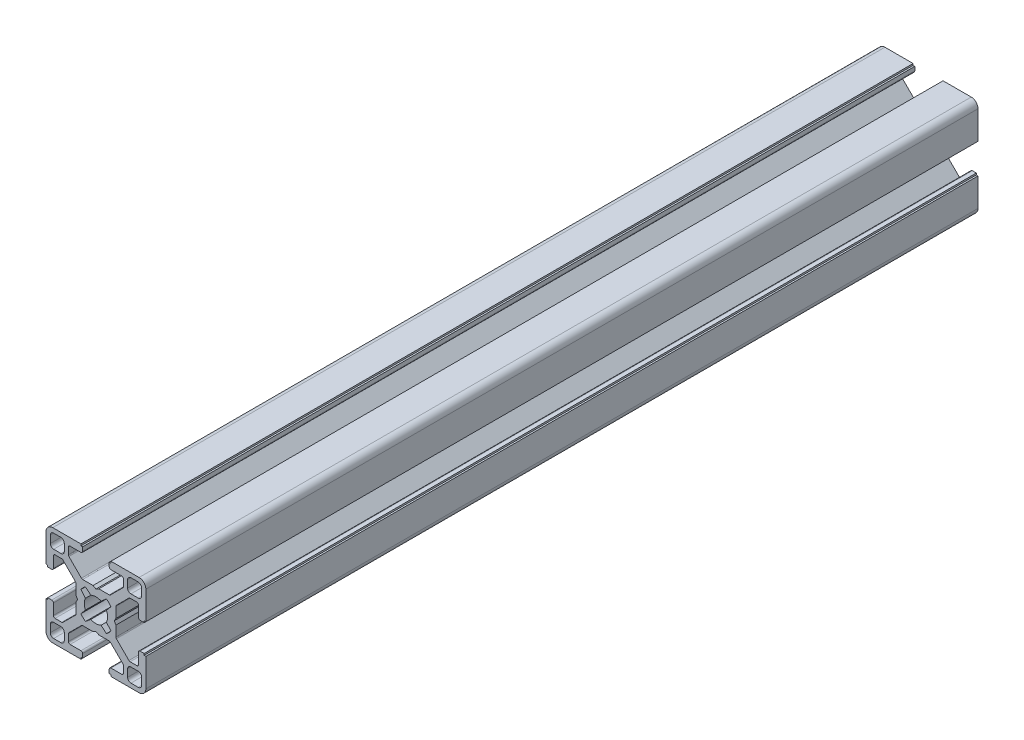
SolidWorks part; units mm, degrees
ref_plane "Front Plane" through (0, 0, 0) normal (0, 0, 1) x (1, 0, 0)
ref_plane "Top Plane" through (0, 0, 0) normal (0, 1, 0) x (1, 0, 0)
ref_plane "Right Plane" through (0, 0, 0) normal (1, 0, 0) x (0, 0, -1)
sketch "Sketch1" plane through (0, 0, 0) normal (0, 0, 1) x (1, 0, 0)
  line L0 (-15, 0) -> (15, 0) construction
  line L1 (0, -15) -> (0, 15) construction
  line L2 (-4.5, 15) -> (4.5, 15) construction
  line L3 (-4, -15) -> (4, -15) construction
  line L4 (-4.5, 15) -> (-4.5, 14.5)
  line L5 (-4.5, 14.5) -> (-4, 14.5)
  line L6 (-4, 14.5) -> (-4, 13.29)
  line L7 (-4.5, 12.79) -> (-7.7675, 12.79)
  line L8 (-8.2675, 12.29) -> (-8.2675, 10.2707)
  line L9 (-8.1211, 9.9171) -> (-4.3504, 6.1464)
  line L10 (-3.9968, 6) -> (0, 6)
  line L11 (0, 0) -> (-15, 15) construction
  line L12 (-4.5, 15) -> (-12.968, 15)
  line L14 (-12.705, 9.5135) -> (-10.5135, 9.5135)
  line L15 (-13.705, 10.5135) -> (-13.705, 12.705)
  line L16 (-12.705, 13.705) -> (-10.5135, 13.705)
  line L17 (-9.5135, 10.5135) -> (-9.5135, 12.705)
  line L18 (-13.705, 9.5135) -> (-9.5135, 13.705) construction
  line L19 (-13.705, 13.705) -> (-9.5135, 9.5135) construction
  line L20 (-3.1568, 4.5038) -> (-1.5303, 3.1477) construction
  line L21 (-4.5038, 3.1568) -> (-3.1477, 1.5303) construction
  line L22 (-6, 3.9968) -> (-6, 0)
  line L23 (-9.9171, 8.1211) -> (-6.1464, 4.3504)
  line L24 (-15, 4.5) -> (-15, 12.968)
  line L25 (-12.29, 8.2675) -> (-10.2707, 8.2675)
  line L26 (-12.79, 4.5) -> (-12.79, 7.7675)
  line L27 (-14.5, 4) -> (-13.29, 4)
  line L28 (-14.5, 4.5) -> (-14.5, 4)
  line L29 (-15, 4.5) -> (-14.5, 4.5)
  circle A0 centre (0, 0) radius 3.5
  arc A1 (-12.968, 15) -> (-15, 12.968) centre (-12.968, 12.968) ccw
  circle A2 centre (0, 0) radius 5.5 construction
  arc A3 (-10.5135, 9.5135) -> (-9.5135, 10.5135) centre (-10.5135, 10.5135) ccw
  arc A4 (-13.705, 12.705) -> (-12.705, 13.705) centre (-12.705, 12.705) cw
  arc A5 (-10.5135, 13.705) -> (-9.5135, 12.705) centre (-10.5135, 12.705) cw
  arc A6 (-12.705, 9.5135) -> (-13.705, 10.5135) centre (-12.705, 10.5135) cw
  arc A7 (-12.79, 4.5) -> (-13.29, 4) centre (-13.29, 4.5) cw
  arc A8 (-12.29, 8.2675) -> (-12.79, 7.7675) centre (-12.29, 7.7675) ccw
  arc A9 (-9.9171, 8.1211) -> (-10.2707, 8.2675) centre (-10.2707, 7.7675) ccw
  arc A10 (-6, 3.9968) -> (-6.1464, 4.3504) centre (-6.5, 3.9968) ccw
  arc A11 (-4.3504, 6.1464) -> (-3.9968, 6) centre (-3.9968, 6.5) ccw
  arc A12 (-4, 13.29) -> (-4.5, 12.79) centre (-4.5, 13.29) cw
  arc A13 (-7.7675, 12.79) -> (-8.2675, 12.29) centre (-7.7675, 12.29) ccw
  arc A14 (-8.2675, 10.2707) -> (-8.1211, 9.9171) centre (-7.7675, 10.2707) ccw
  point P4 (0, 0)
  point P8 (0, 0)
  point P13 (0, 15)
  point P15 (0, -15)
  point P16 (0, 6)
  point P23 (-11.6092, 11.6093)
  point P26 (0, 6)
  point P62 (-12.79, 4)
  point P65 (-12.79, 8.2675)
  point P68 (-10.0636, 8.2675)
  point P71 (-6, 4.2039)
  point P74 (-4.2039, 6)
  point P77 (-4, 12.79)
  point P80 (-8.2675, 12.79)
  point P83 (-8.2675, 10.0636)
  dimension "Center Hole Diameter" = 7
  dimension "D11" = 2.032
  dimension "D9" = 11
  dimension "D13" = 1
  dimension "D14" = 0.5
  dimension "Rail Height" = 30
  dimension "Rail Width" = 30
  dimension "T-Slot Width" = 8
  dimension "T-Slot Depth" = 9
  dimension "D1" = 9
  dimension "D2" = 45
  dimension "D3" = 8
  dimension "D4" = 2.21
  dimension "D5" = 16.535
  dimension "D7" = 2.54
  dimension "D6" = 1.295
  dimension "D8" = 1.246
  dimension "D10" = 10.36
  dimension "D12" = 1.905
sketch "Sketch2" plane through (0, 0, 0) normal (1, 0, 0) x (0, 0, -1)
  line L0 (-76.2, 0) -> (76.2, 0) construction
  line L2 (0, -15) -> (0, 15) construction
  line L3 (0, -15) -> (0, 15) construction
  line L4 (-76.2, -15) -> (-76.2, 15) construction
  line L5 (76.2, -15) -> (76.2, 15) construction
  point P0 (-38.7, 0)
  point P3 (0, 0)
  point P4 (38.7, 0)
  point P12 (-76.2, 0)
  point P14 (76.2, 0)
  dimension "Length" = 152.4
  dimension "D1" = 37.5
sketch "Sketch3" plane through (0, 0, 0) normal (0, 0, 1) x (1, 0, 0)
  line L0 (-4.5038, 3.1568) -> (-3.1477, 1.5303)
  line L1 (0, 3.5) -> (0, 5.5)
  line L2 (-5.5, 0) -> (-3.5, 0)
  line L7 (-6, 3.9968) -> (-6, 0) construction
  line L31 (-9.9171, 8.1211) -> (-6.1464, 4.3504) construction
  line L117 (-12.29, 8.2675) -> (-10.2707, 8.2675) construction
  line L118 (-12.79, 4.5) -> (-12.79, 7.7675) construction
  line L157 (-12.705, 9.5135) -> (-10.5135, 9.5135)
  line L158 (-9.5135, 10.5135) -> (-9.5135, 12.705)
  line L163 (-10.5135, 13.705) -> (-12.705, 13.705)
  line L164 (-13.705, 12.705) -> (-13.705, 10.5135)
  line L165 (-12.705, 9.5135) -> (-10.5135, 9.5135)
  line L166 (-9.5135, 10.5135) -> (-9.5135, 12.705)
  line L167 (-10.5135, 13.705) -> (-12.705, 13.705)
  line L168 (-13.705, 12.705) -> (-13.705, 10.5135)
  line L169 (-14.5, 4) -> (-13.29, 4) construction
  line L170 (-14.5, 4.5) -> (-14.5, 4) construction
  line L171 (-15, 4.5) -> (-14.5, 4.5) construction
  line L172 (-15, 4.5) -> (-15, 12.968) construction
  line L173 (-4.5, 15) -> (-12.968, 15) construction
  line L174 (-4.5, 15) -> (-4.5, 14.5) construction
  line L175 (-4.5, 14.5) -> (-4, 14.5) construction
  line L176 (-4, 14.5) -> (-4, 13.29) construction
  line L177 (-4.5, 12.79) -> (-7.7675, 12.79) construction
  line L178 (-8.2675, 12.29) -> (-8.2675, 10.2707) construction
  line L179 (-8.1211, 9.9171) -> (-4.3504, 6.1464) construction
  line L180 (-3.9968, 6) -> (0, 6) construction
  line L181 (-6, 3.9968) -> (-6, 0.866)
  line L182 (-9.9171, 8.1211) -> (-6.1464, 4.3504)
  line L183 (-12.29, 8.2675) -> (-10.2707, 8.2675)
  line L184 (-12.79, 4.5) -> (-12.79, 7.7675)
  line L185 (-14.5, 4) -> (-13.29, 4)
  line L186 (-14.5, 4.5) -> (-14.5, 4)
  line L187 (-15, 4.5) -> (-14.5, 4.5)
  line L188 (-15, 4.5) -> (-15, 12.968)
  line L189 (-4.5, 15) -> (-12.968, 15)
  line L190 (-4.5, 15) -> (-4.5, 14.5)
  line L191 (-4.5, 14.5) -> (-4, 14.5)
  line L192 (-4, 14.5) -> (-4, 13.29)
  line L193 (-4.5, 12.79) -> (-7.7675, 12.79)
  line L194 (-8.2675, 12.29) -> (-8.2675, 10.2707)
  line L195 (-8.1211, 9.9171) -> (-4.3504, 6.1464)
  line L196 (-3.9968, 6) -> (-0.866, 6)
  line L197 (-0.866, 6) -> (0, 5.5)
  line L198 (0, -15) -> (0, 15) construction
  line L199 (0, 0) -> (-15, 15) construction
  line L200 (0, 0) -> (-15, 15) construction
  line L201 (-3.1568, 4.5038) -> (-1.5303, 3.1477) construction
  line L202 (-3.1568, 4.5038) -> (-1.5303, 3.1477)
  line L203 (-6, 0.866) -> (-5.5, 0)
  line L204 (-15, 0) -> (15, 0) construction
  line L205 (-15, 0) -> (15, 0) construction
  line L206 (0, -15) -> (0, 15) construction
  arc A0 (-3.5, 0) -> (-3.1477, 1.5303) centre (0, 0) cw
  arc A10 (-6, 3.9968) -> (-6.1464, 4.3504) centre (-6.5, 3.9968) ccw construction
  circle A16 centre (0, 0) radius 3.5
  arc A18 (0, 3.5) -> (-1.5303, 3.1477) centre (0, 0) ccw
  arc A20 (-9.9171, 8.1211) -> (-10.2707, 8.2675) centre (-10.2707, 7.7675) ccw construction
  arc A22 (-12.29, 8.2675) -> (-12.79, 7.7675) centre (-12.29, 7.7675) ccw construction
  arc A28 (-13.29, 4) -> (-12.79, 4.5) centre (-13.29, 4.5) ccw construction
  arc A29 (-10.5135, 9.5135) -> (-9.5135, 10.5135) centre (-10.5135, 10.5135) ccw
  arc A30 (-9.5135, 12.705) -> (-10.5135, 13.705) centre (-10.5135, 12.705) ccw
  arc A31 (-12.705, 13.705) -> (-13.705, 12.705) centre (-12.705, 12.705) ccw
  arc A32 (-13.705, 10.5135) -> (-12.705, 9.5135) centre (-12.705, 10.5135) ccw
  arc A33 (-10.5135, 9.5135) -> (-9.5135, 10.5135) centre (-10.5135, 10.5135) ccw
  arc A34 (-9.5135, 12.705) -> (-10.5135, 13.705) centre (-10.5135, 12.705) ccw
  arc A35 (-12.705, 13.705) -> (-13.705, 12.705) centre (-12.705, 12.705) ccw
  arc A36 (-13.705, 10.5135) -> (-12.705, 9.5135) centre (-12.705, 10.5135) ccw
  arc A37 (-12.968, 15) -> (-15, 12.968) centre (-12.968, 12.968) ccw construction
  arc A38 (-4.5, 12.79) -> (-4, 13.29) centre (-4.5, 13.29) ccw construction
  arc A39 (-7.7675, 12.79) -> (-8.2675, 12.29) centre (-7.7675, 12.29) ccw construction
  arc A40 (-8.2675, 10.2707) -> (-8.1211, 9.9171) centre (-7.7675, 10.2707) ccw construction
  arc A41 (-4.3504, 6.1464) -> (-3.9968, 6) centre (-3.9968, 6.5) ccw construction
  arc A42 (-6, 3.9968) -> (-6.1464, 4.3504) centre (-6.5, 3.9968) ccw
  arc A43 (-9.9171, 8.1211) -> (-10.2707, 8.2675) centre (-10.2707, 7.7675) ccw
  arc A44 (-12.29, 8.2675) -> (-12.79, 7.7675) centre (-12.29, 7.7675) ccw
  arc A45 (-13.29, 4) -> (-12.79, 4.5) centre (-13.29, 4.5) ccw
  arc A46 (-12.968, 15) -> (-15, 12.968) centre (-12.968, 12.968) ccw
  arc A47 (-4.5, 12.79) -> (-4, 13.29) centre (-4.5, 13.29) ccw
  arc A48 (-7.7675, 12.79) -> (-8.2675, 12.29) centre (-7.7675, 12.29) ccw
  arc A49 (-8.2675, 10.2707) -> (-8.1211, 9.9171) centre (-7.7675, 10.2707) ccw
  arc A50 (-4.3504, 6.1464) -> (-3.9968, 6) centre (-3.9968, 6.5) ccw
  circle A51 centre (0, 0) radius 5.5 construction
  arc A52 (-3.1568, 4.5038) -> (-4.5038, 3.1568) centre (0, 0) ccw
  dimension "D3" = 60
  dimension "D4" = 60
  dimension "D1" = 0
  dimension "D2" = 0
extrude "Boss-Extrude1" add sketch "Sketch3" along normal mid plane 250
pattern_circular "CirPattern1" count 4 over 360 about axis through (0, 0, 76.2) along (0, 0, -1) of "Boss-Extrude1"
ref_plane "Contact Plane1" through (15, 0, 0) normal (1, 0, 0) x (0, 0, -1)
ref_plane "Contact Plane2" through (0, -15, 0) normal (0, 1, 0) x (1, 0, 0)
ref_plane "Contact Plane3" through (-15, 0, 0) normal (1, 0, 0) x (0, 0, -1)
ref_plane "Contact Plane4" through (0, 15, 0) normal (0, 1, 0) x (1, 0, 0)
equation "\"D1@Sketch2\" = \"Rail Height@Sketch1\" * 1.25"
equation "\"D1@Sketch1\"=\"T-Slot Width@Sketch1\"+1mm"
equation "\"D3@Sketch1\"=\"T-Slot Width@Sketch1\""
equation "\"D1@Boss-Extrude1\"=\"Width\""
equation "\"Width\"= 250mm"
